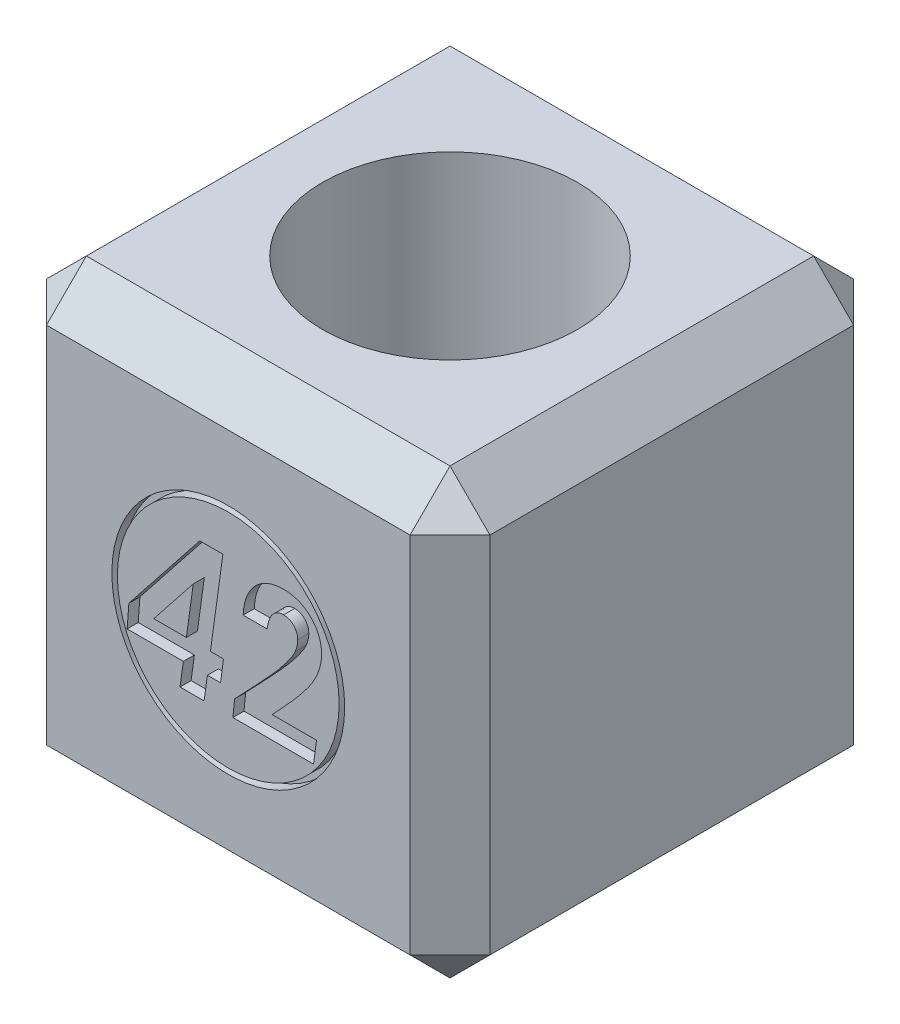
SolidWorks part; units mm, degrees
ref_plane "Front" through (0, 0, 0) normal (0, 0, 1) x (1, 0, 0)
ref_plane "Top" through (0, 0, 0) normal (0, 1, 0) x (1, 0, 0)
ref_plane "Right" through (0, 0, 0) normal (1, 0, 0) x (0, 0, -1)
sketch "草图1" plane through (0, 0, 0) normal (1, 0, 0) x (0, 0, -1)
  line L1 (0, 0) -> (200, 0)
  line L2 (0, 0) -> (0, 200)
  line L3 (0, 200) -> (200, 200)
  line L4 (200, 0) -> (200, 200)
  dimension "D1" = 200
  dimension "D2" = 200
extrude "凸台-拉伸1" add sketch "草图1" along normal blind 200
chamfer "倒角1" distance 18 angle 45 12 edges at (0, 100, -200) (100, 0, -200) (0, 0, -100) (200, 100, -200) (200, 0, -100) (200, 100, 0) (100, 0, 0) (0, 100, 0) (100, 200, -200) (200, 200, -100) (100, 200, 0) (0, 200, -100)
sketch "草图2" plane through (0, 200, 0) normal (0, 1, 0) x (1, 0, 0)
  line L0 (0, 18) -> (0, 182) construction
  line L1 (18, 200) -> (182, 200) construction
  circle A0 centre (100, 100) radius 57.5
  point P5 (0, 100)
  point P8 (100, 200)
  dimension "D1" = 115
extrude "切除-拉伸1" cut sketch "草图2" against normal blind 150
sketch "草图3" plane through (0, 0, 0) normal (0, 0, 1) x (1, 0, 0)
  line L0 (0, 18) -> (0, 182) construction
  line L1 (18, 200) -> (182, 200) construction
  line L2 (87.1403, 132.3118) -> (97.585, 132.3118)
  line L3 (97.585, 132.3118) -> (91.96, 91.5425)
  line L4 (91.96, 91.5425) -> (97.8374, 91.5425)
  line L5 (97.8374, 91.5425) -> (96.5393, 81.5425)
  line L6 (96.5393, 81.5425) -> (90.5898, 81.5425)
  line L7 (90.5898, 81.5425) -> (89.0994, 70.7733)
  line L8 (89.0994, 70.7733) -> (78.2461, 70.7733)
  line L9 (78.2461, 70.7733) -> (79.7365, 81.5425)
  line L10 (79.7365, 81.5425) -> (54.3999, 81.5425)
  line L11 (54.3999, 81.5425) -> (55.1692, 91.9512)
  line L12 (55.1692, 91.9512) -> (87.1403, 132.3118)
  line L13 (84.2076, 114.0185) -> (66.4071, 91.5425)
  line L14 (66.4071, 91.5425) -> (81.1067, 91.5425)
  line L15 (81.1067, 91.5425) -> (84.2076, 114.0185)
  line L16 (117.4768, 113.081) -> (106.7076, 113.081)
  line L17 (119.7845, 80.7733) -> (139.7845, 80.7733)
  line L18 (139.7845, 80.7733) -> (138.4624, 70.7733)
  line L19 (138.4624, 70.7733) -> (102.0922, 70.7733)
  line L20 (102.0922, 70.7733) -> (102.8615, 78.4656)
  circle A0 centre (100, 100) radius 50
  circle A1 centre (100, 100) radius 52.5
  spline S0 degree 3 poles (106.7076, 113.081) (106.7819, 114.9376) (107.1315, 117.6647) (108.2378, 121.0704) (109.3025, 123.3705) (110.6134, 125.4421) (112.1325, 127.268) (113.8756, 128.8061) (115.7959, 130.093) (117.8958, 131.0883) (120.9374, 132.0577) (123.3582, 132.3062) (124.9889, 132.3118) knots 0 0 0 0 0.188116 0.275893 0.361278 0.44379 0.523169 0.600667 0.678099 0.756216 0.8349 1 1 1 1
  spline S1 degree 3 poles (124.9889, 132.3118) (126.1758, 132.3157) (127.935, 132.1795) (130.1867, 131.6551) (131.7727, 131.1293) (133.2685, 130.4378) (134.6873, 129.6025) (136.0263, 128.6134) (137.2653, 127.4763) (138.3907, 126.2317) (139.3848, 124.9022) (140.2284, 123.4994) (140.9069, 122.0136) (141.4346, 120.4586) (141.9593, 118.2551) (142.0955, 116.5356) (142.0922, 115.3767) knots 0 0 0 0 0.132319 0.195567 0.257266 0.318197 0.378842 0.440456 0.503345 0.565934 0.62719 0.688063 0.747996 0.808849 0.870793 1 1 1 1
  spline S2 degree 3 poles (142.0922, 115.3767) (142.0973, 114.3935) (141.9543, 112.9056) (141.5811, 110.9151) (141.1482, 109.3783) (140.6245, 107.8018) (139.9675, 106.1991) (139.1991, 104.5654) (138.4552, 103.1833) (137.7797, 102.028) (137.1718, 101.0902) (136.4908, 100.0813) (135.7113, 99.0106) (134.8669, 97.8548) (133.9101, 96.6451) (132.8802, 95.3632) (131.7712, 94.0089) (130.5674, 92.5954) (129.285, 91.1058) (127.9111, 89.5507) (126.4434, 87.9366) (124.9064, 86.2331) (122.6792, 83.8367) (120.9671, 82.0033) (119.7845, 80.7733) knots 0 0 0 0 0.069982 0.106337 0.144238 0.183709 0.224709 0.26764 0.312365 0.336564 0.363027 0.392021 0.423332 0.457436 0.49406 0.53327 0.574668 0.618847 0.665627 0.714798 0.76677 0.821162 0.878361 1 1 1 1
  spline S3 degree 3 poles (102.8615, 78.4656) (104.0731, 79.7379) (105.8614, 81.588) (108.1581, 84.0301) (109.7744, 85.7196) (111.2922, 87.3424) (112.7422, 88.8734) (114.109, 90.3193) (115.3818, 91.6945) (116.5785, 92.9783) (117.6738, 94.1976) (118.7173, 95.307) (119.6507, 96.3561) (120.5036, 97.3216) (121.4959, 98.4225) (122.1726, 99.2301) (122.6091, 99.7276) knots 0 0 0 0 0.181614 0.265988 0.346549 0.423312 0.495675 0.564526 0.628996 0.689369 0.745951 0.798411 0.846804 0.891103 0.931584 1 1 1 1
  spline S4 degree 3 poles (122.6091, 99.7276) (123.5425, 100.8553) (124.8846, 102.4745) (126.4948, 104.6189) (127.5229, 106.0155) (128.3907, 107.3106) (129.3062, 108.7645) (129.869, 109.828) (130.1571, 110.5089) knots 0 0 0 0 0.332832 0.477817 0.60952 0.726973 0.8321 1 1 1 1
  spline S5 degree 3 poles (130.1571, 110.5089) (130.5118, 111.3661) (131.1204, 113.0574) (131.3197, 114.8452) (131.323, 115.7012) knots 0 0 0 0 0.520562 1 1 1 1
  spline S6 degree 3 poles (131.323, 115.7012) (131.3028, 116.5792) (131.1363, 117.9147) (130.3065, 119.455) (129.5007, 120.4508) (128.5388, 121.2773) (127.0618, 122.1011) (125.7928, 122.3045) (124.9528, 122.3118) knots 0 0 0 0 0.259694 0.383137 0.508398 0.633351 0.752658 1 1 1 1
  spline S7 degree 3 poles (124.9528, 122.3118) (124.0619, 122.3161) (122.7233, 122.0653) (121.1598, 121.1773) (120.3181, 120.4048) (119.7118, 119.6616) (119.2997, 118.9924) (118.8906, 118.2461) (118.558, 117.3873) (118.2254, 116.4486) (117.8367, 115.009) (117.5875, 113.8761) (117.4768, 113.081) knots 0 0 0 0 0.204128 0.304431 0.408409 0.463887 0.523727 0.588196 0.658594 0.734358 0.816313 1 1 1 1
  point P5 (0, 100)
  point P8 (100, 200)
  dimension "D1" = 100
  dimension "D2" = 105
extrude "切除-拉伸4" cut sketch "草图3" against normal blind 5 contours L12 L11 L10 L9 L8 L7 L6 L5 L4 L3 L2 L15 L14 L13 | S7 S6 S5 S4 S3 L20 L19 L18 L17 S2 S1 S0 L16 | A1 A0 region at (92.3627, 131.5585, 0) region at (123.9634, 99.6003, 0) region at (48.9849, 100, 0)
ref_plane "基准面1" through (0, 0, -100) normal (0, 0, 1) x (1, 0, 0)
ref_plane "基准面2" through (0, 100, 0) normal (0, 1, 0) x (1, 0, 0)
ref_axis "基准轴1" through (190.2, 100, -100) along (-1, 0, 0)
ref_plane "基准面3" through (0, 125, 0) normal (0, 1, 0) x (1, 0, 0)
ref_axis "基准轴2" through (190.2, 125, -100) along (-1, 0, 0)
